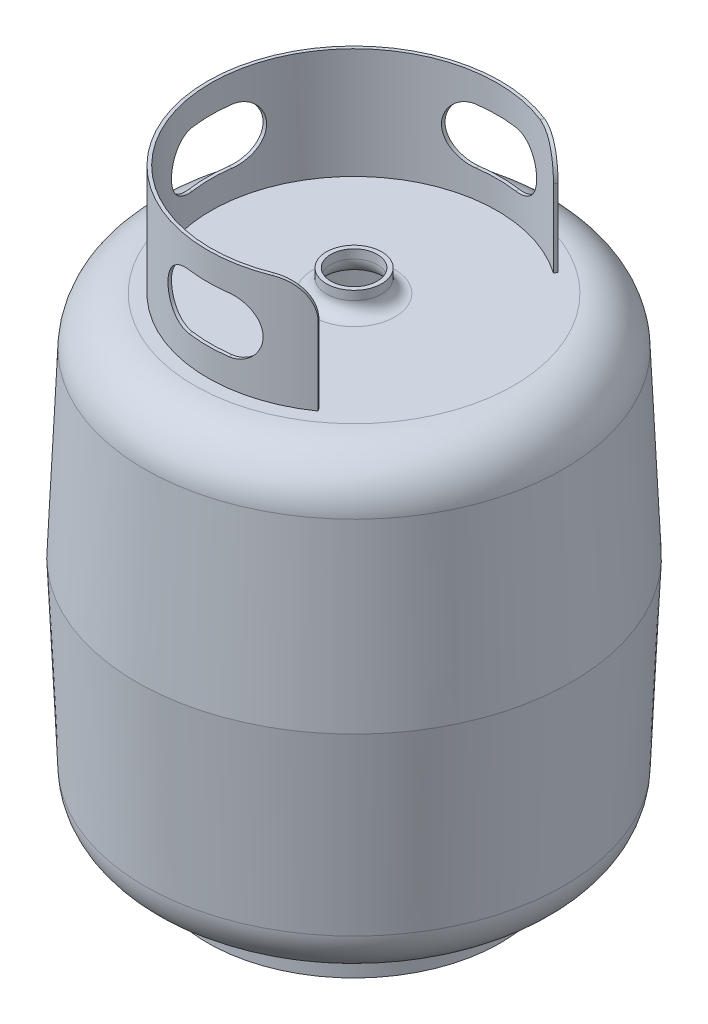
SolidWorks part; units mm, degrees
material "1060 Alloy"
ref_plane "Front Plane" through (0, 0, 0) normal (0, 0, 1) x (1, 0, 0)
ref_plane "Top Plane" through (0, 0, 0) normal (0, 1, 0) x (1, 0, 0)
ref_plane "Right Plane" through (0, 0, 0) normal (1, 0, 0) x (0, 0, -1)
sketch "Sketch1" plane through (0, 0, 0) normal (0, 0, 1) x (1, 0, 0)
  line L0 (0, 206.25) -> (0, -206.25) construction
  line L1 (0, -206.25) -> (144.4219, -206.25)
  line L2 (189.379, -163.2129) -> (196.5051, 0)
  line L3 (196.5051, 0) -> (0, 0) construction
  line L4 (37, 206.25) -> (144.4219, 206.25)
  line L5 (189.379, 163.2129) -> (196.5051, 0)
  line L6 (25, 218.25) -> (25, 226.25)
  line L7 (25, 226.25) -> (0, 226.25)
  line L8 (0, 226.25) -> (0, -206.25)
  arc A0 (144.4219, -206.25) -> (189.379, -163.2129) centre (144.4219, -161.25) ccw
  arc A1 (144.4219, 206.25) -> (189.379, 163.2129) centre (144.4219, 161.25) cw
  arc A2 (25, 218.25) -> (37, 206.25) centre (37, 218.25) ccw
  point P3 (0, 0)
  point P9 (187.5, -206.25)
  point P18 (25, 206.25)
  dimension "D4" = 45
  dimension "D6" = 45
  dimension "D9" = 12
  dimension "D1" = 92.5
  dimension "D2" = 412.5
  dimension "D3" = 375
  dimension "D5" = 92.5
  dimension "D7" = 20
  dimension "D8" = 50
revolve "Revolve1" add sketch "Sketch1" angle 360 about L8 region at (94.645, 1.4514, 0)
shell "Shell1" thickness 4 removed face at (-25, 226.25, 0)
sketch "Sketch3" plane through (0, 206.25, 0) normal (0, 1, 0) x (1, 0, 0)
  line L0 (0, 0) -> (75.9541, 108.4736) construction
  line L1 (0, 0) -> (174.3445, 0) construction
  line L2 (0, 0) -> (75.9541, -108.4736) construction
  line L3 (75.9541, 108.4736) -> (74.2333, 106.0162)
  line L4 (74.2333, -106.0162) -> (75.9541, -108.4736)
  arc A0 (75.9541, 108.4736) -> (75.9541, -108.4736) centre (0, 0) ccw
  circle A1 centre (0, 0) radius 144.4219 construction
  arc A2 (74.2333, 106.0162) -> (74.2333, -106.0162) centre (0, 0) ccw
  circle A3 centre (0, 0) radius 132.4219 construction
  circle A4 centre (0, 0) radius 129.4219 construction
  dimension "D1" = 12
  dimension "D3" = 55
  dimension "D4" = 55
  dimension "D2" = 3
extrude "Boss-Extrude1" add sketch "Sketch3" along normal blind 100
fillet "Fillet1" radius 30 2 edges at (75.0937, 306.25, 107.2449) (75.0937, 306.25, -107.2449)
sketch "Sketch4" plane through (0, 0, 0) normal (0, 0, 1) x (1, 0, 0)
  line L0 (49.4047, 306.25) -> (-132.4219, 306.25) construction
  line L3 (-18, 256.25) -> (18, 256.25) construction
  line L4 (-18, 281.25) -> (18, 281.25)
  line L5 (-18, 231.25) -> (18, 231.25)
  arc A0 (-18, 281.25) -> (-18, 231.25) centre (-18, 256.25) ccw
  arc A1 (18, 231.25) -> (18, 281.25) centre (18, 256.25) ccw
  point P8 (0, 256.25)
  dimension "D1" = 18
  dimension "D2" = 50
  dimension "D3" = 50
extrude "Cut-Extrude1" cut sketch "Sketch4" against normal through all and the other way through all contours A0 L5 A1 L4
sketch "Sketch5" plane through (0, 0, 0) normal (1, 0, 0) x (0, 0, -1)
  line L0 (-18, 256.25) -> (18, 256.25) construction
  line L1 (-18, 281.25) -> (18, 281.25)
  line L2 (-18, 231.25) -> (18, 231.25)
  line L3 (129.4219, 306.25) -> (-129.4219, 306.25) construction
  arc A0 (-18, 281.25) -> (-18, 231.25) centre (-18, 256.25) ccw
  arc A1 (18, 231.25) -> (18, 281.25) centre (18, 256.25) ccw
  point P2 (0, 256.25)
  dimension "D2" = 50
  dimension "D1" = 18
  dimension "D3" = 50
extrude "Cut-Extrude2" cut sketch "Sketch5" against normal up to surface (131.1928 mm away) up to face at (0, 256.25, -128.8685)
sketch "Sketch6" plane through (0, -206.25, 0) normal (0, -1, 0) x (1, 0, 0)
  circle A0 centre (0, 0) radius 132.4219
  circle A1 centre (0, 0) radius 144.4219 construction
  circle A2 centre (0, 0) radius 129.4219
  dimension "D1" = 12
  dimension "D2" = 3
extrude "Boss-Extrude2" add sketch "Sketch6" along normal blind 30
